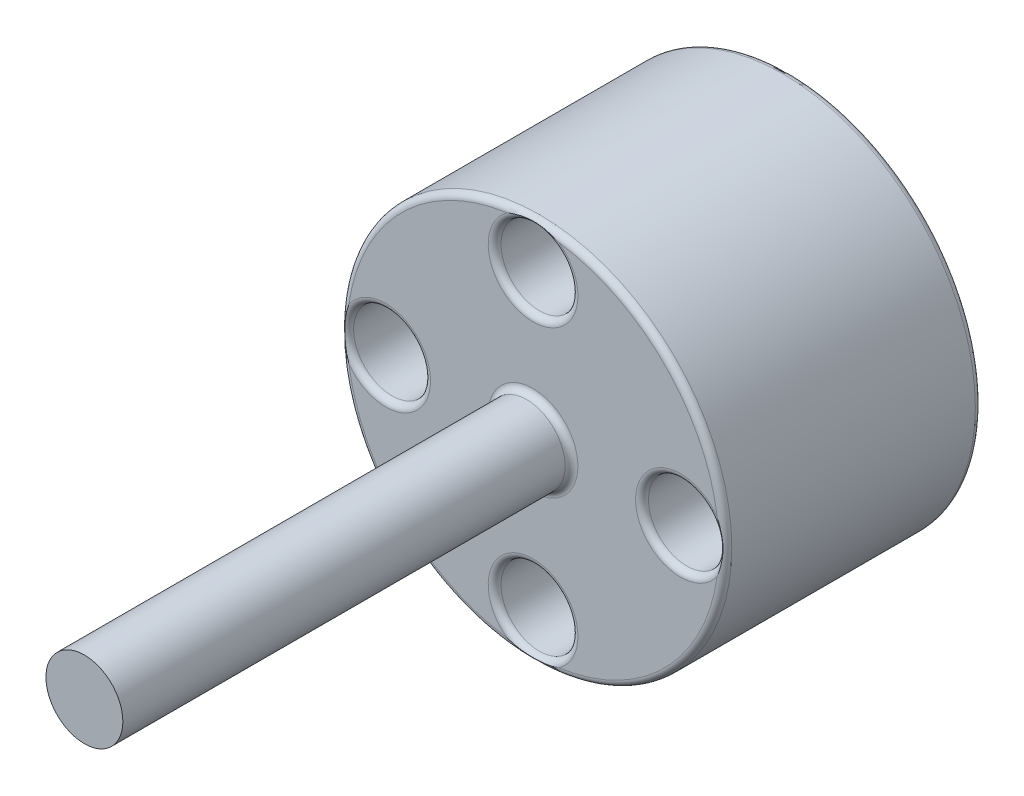
SolidWorks part; units mm, degrees
material "Custom Plastic"
ref_plane "Спереди" through (0, 0, 0) normal (0, 0, 1) x (1, 0, 0)
ref_plane "Сверху" through (0, 0, 0) normal (0, 1, 0) x (1, 0, 0)
ref_plane "Справа" through (0, 0, 0) normal (1, 0, 0) x (0, 0, -1)
sketch "Sketch1" plane through (0, 0, 0) normal (0, 0, 1) x (1, 0, 0)
  circle A0 centre (0, 0) radius 1.5
  dimension "D1" = 3
extrude "Boss-Extrude1" add sketch "Sketch1" along normal blind 2
sketch "Sketch2" plane through (0, 0, 2) normal (0, 0, 1) x (1, 0, 0)
  circle A0 centre (0, 0) radius 0.3
sketch "Sketch3" plane through (0, 0, 2) normal (0, 0, 1) x (1, 0, 0)
  circle A0 centre (0, 1.15) radius 0.3
  circle A1 centre (1.15, 0) radius 0.3
  circle A2 centre (0, -1.15) radius 0.3
  circle A3 centre (0, 0) radius 1.5 construction
  circle A5 centre (-1.15, 0) radius 0.3
  point P13 (0, 0)
  dimension "D1" = 4
  dimension "D7" = 1.15
extrude "Cut-Extrude2" cut sketch "Sketch3" against normal blind 3
extrude "Boss-Extrude2" add sketch "Sketch2" against normal blind 2 and the other way blind 3.5 contours A0
fillet "Fillet1" radius 0.05 11 edges at (0.3, 1.15, 2) (-0.85, 0, 2) (1.45, 0, 2) (0.3, -1.15, 2) (0.3, 0, 2) (1.5, 0, 0) (1.5, 0, 2) (0.3, 1.15, 0) (-0.85, 0, 0) (1.45, 0, 0) (0.3, -1.15, 0)
